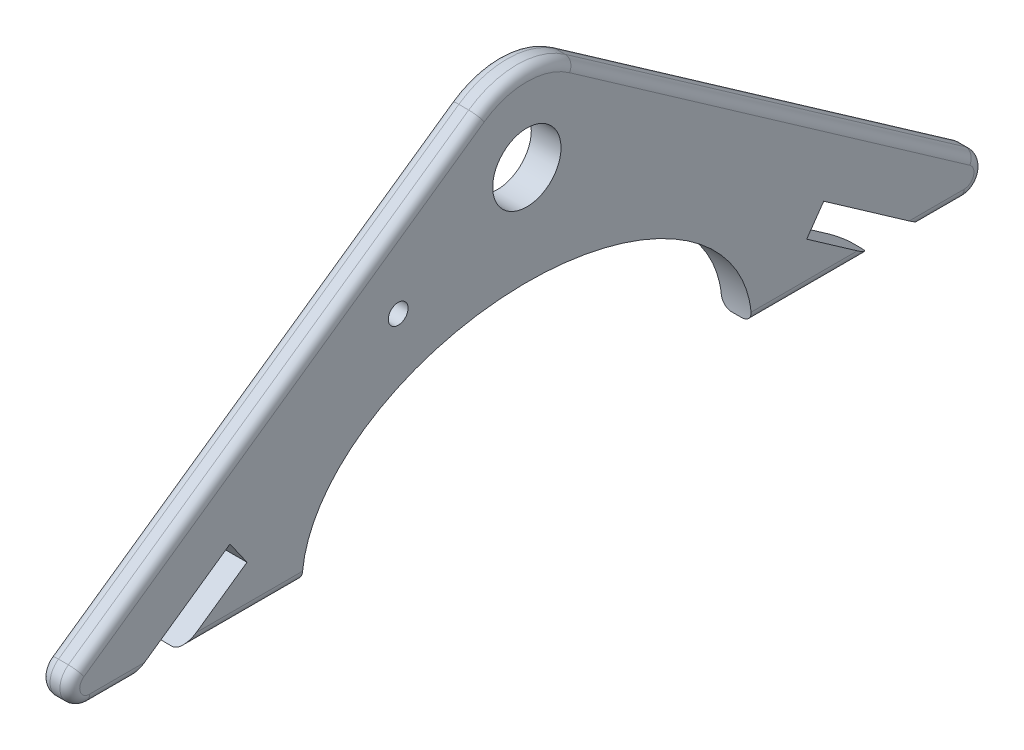
SolidWorks part; units mm, degrees
ref_plane "Front Plane" through (0, 0, 0) normal (0, 0, 1) x (1, 0, 0)
ref_plane "Top Plane" through (0, 0, 0) normal (0, 1, 0) x (1, 0, 0)
ref_plane "Right Plane" through (0, 0, 0) normal (1, 0, 0) x (0, 0, -1)
sketch "Sketch1" plane through (0, 0, 0) normal (1, 0, 0) x (0, 0, -1)
  line L0 (0, 0) -> (0, 9.7181) construction
  line L1 (0, 0) -> (-4.8754, 6.9628) construction
  line L2 (-4.8754, 6.9628) -> (-45.327, -21.3617)
  line L3 (0, 0) -> (0, -25) construction
  line L4 (-22.712, -25) -> (-34.832, -25)
  line L5 (-40.0623, -25) -> (-29.9995, -17.9539)
  line L6 (-40.0623, -25) -> (-44.1798, -25)
  line L7 (-29.9995, -17.9539) -> (-28.2788, -20.4114)
  line L8 (-34.832, -25) -> (-28.2788, -20.4114)
  line L9 (-38.4724, -16.5621) -> (-35.0309, -21.477) construction
  line L10 (0, 0) -> (-13.001, -6.307) construction
  line L11 (34.832, -25) -> (28.2788, -20.4114)
  line L12 (0, -25) -> (0, -7) construction
  line L13 (-16.5625, -1.2206) -> (-9.4394, -11.3933) construction
  line L15 (29.9995, -17.9539) -> (28.2788, -20.4114)
  line L16 (40.0623, -25) -> (44.1798, -25)
  line L17 (40.0623, -25) -> (29.9995, -17.9539)
  line L18 (22.712, -25) -> (34.832, -25)
  line L19 (4.8754, 6.9628) -> (45.327, -21.3617)
  line L20 (-50.523, -25) -> (-22.712, -25) construction
  arc A0 (4.8754, 6.9628) -> (-4.8754, 6.9628) centre (0, 0) ccw
  circle A1 centre (0, 0) radius 3.45
  arc A2 (45.327, -21.3617) -> (44.1798, -25) centre (44.1798, -23) cw
  arc A3 (-45.327, -21.3617) -> (-44.1798, -25) centre (-44.1798, -23) ccw
  circle A4 centre (-13.001, -6.307) radius 1
  ellipse E0 centre (0, -25) end of major axis (-22.712, -25) minor radius 14.9599 (22.712, -25) -> (-22.712, -25) ccw
  point P24 (50.523, -25)
  point P25 (50.523, -25)
  point P36 (-13.001, -6.307)
  dimension "D1" = 8.5
  dimension "D9" = 6.9
  dimension "D10" = 2
  dimension "D5" = 14.45
  dimension "D2" = 25
  dimension "D3" = 35
  dimension "D4" = 6
  dimension "D6" = 3
  dimension "D7" = 8
extrude "Boss-Extrude1" add sketch "Sketch1" along normal blind 3
fillet "Fillet1" radius 1 18 edges at (0, -25, -42.1211) (0, -7.1995, -25.1012) (0, 8.5, 0) (0, -25, 42.1211) (3, -25, -42.1211) (3, -7.1995, -25.1012) (3, 8.5, 0) (3, -25, 42.1211) (0, -25, -28.772) (3, -25, -28.772) (0, -25, 28.772) (3, -25, 28.772) (0, -7.1995, 25.1012) (3, -7.1995, 25.1012) (0, -23.6014, -46.0872) (0, -23.6014, 46.0872) (3, -23.6014, -46.0872) (3, -23.6014, 46.0872)
